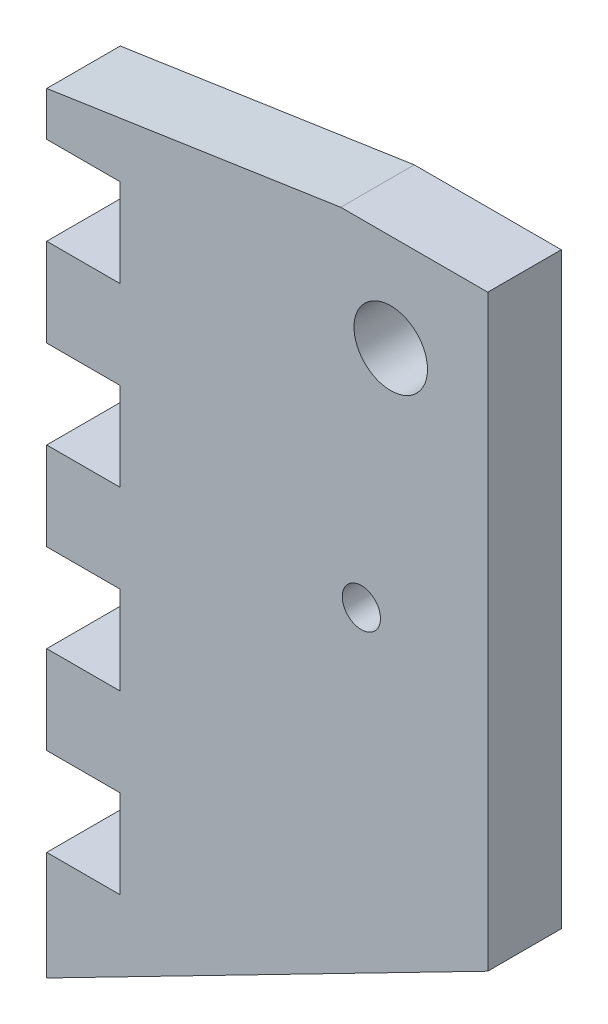
SolidWorks part; units mm, degrees
ref_plane "Front Plane" through (0, 0, 0) normal (0, 0, 1) x (1, 0, 0)
ref_plane "Top Plane" through (0, 0, 0) normal (0, 1, 0) x (1, 0, 0)
ref_plane "Right Plane" through (0, 0, 0) normal (1, 0, 0) x (0, 0, -1)
sketch "Sketch1" plane through (0, 0, 0) normal (0, 0, 1) x (1, 0, 0)
  line L0 (0, 0) -> (-38.1, 0)
  line L1 (0, 0) -> (0, -50.8)
  line L2 (-38.1, 0) -> (-38.1, -7.62)
  line L3 (-38.1, -7.62) -> (-31.75, -7.62)
  line L4 (-31.75, -7.62) -> (-31.75, -15.24)
  line L5 (-31.75, -15.24) -> (-38.1, -15.24)
  line L6 (-38.1, -45.72) -> (-38.1, -70.358)
  line L7 (-38.1, -15.24) -> (-38.1, -22.86)
  line L8 (-38.1, -22.86) -> (-31.75, -22.86)
  line L9 (-31.75, -22.86) -> (-31.75, -30.48)
  line L10 (-31.75, -30.48) -> (-38.1, -30.48)
  line L11 (-38.1, -30.48) -> (-38.1, -38.1)
  line L12 (-38.1, -38.1) -> (-31.75, -38.1)
  line L13 (-31.75, -38.1) -> (-31.75, -45.72)
  line L14 (-31.75, -45.72) -> (-38.1, -45.72)
  line L15 (-38.1, -70.358) -> (0, -50.8)
  circle A0 centre (-8.382, -8.382) radius 3.175
  dimension "D9" = 6.35
  dimension "D1" = 38.1
  dimension "D2" = 50.8
  dimension "D3" = 7.62
  dimension "D4" = 7.62
  dimension "D5" = 6.35
  dimension "D6" = 6.35
  dimension "D8" = 70.358
  dimension "D12" = 8.382
  dimension "D13" = 8.382
  dimension "D7" = 3
extrude "Boss-Extrude1" add sketch "Sketch1" along normal blind 6.35 contours L6 L15 L1 L0 L2 L3 L4 L5 L7 L8 L9 L10 L11 L12 L13 L14 A0 region at (-19.2374, -31.1465, 0)
sketch "Sketch2" plane through (0, 0, 0) normal (0, 0, -1) x (-1, 0, 0)
  line L5 (38.1, 0) -> (12.7, 0)
  line L6 (0, 0) -> (38.1, 0) construction
  line L7 (12.7, 0) -> (38.1, -3.81)
  line L8 (38.1, 0) -> (38.1, -7.62) construction
  line L9 (38.1, -3.81) -> (38.1, 0)
  dimension "D1" = 25.4
  dimension "D2" = 3.81
extrude "Cut-Extrude1" cut sketch "Sketch2" against normal blind 8.636
sketch "Sketch4" plane through (0, 0, 6.35) normal (0, 0, 1) x (1, 0, 0)
  line L0 (-38.1, -45.72) -> (-38.1, -53.34)
  line L1 (-38.1, -45.72) -> (-38.1, -70.358) construction
  line L2 (-38.1, -53.34) -> (-31.75, -53.34)
  line L3 (-31.75, -53.34) -> (-31.75, -60.96)
  line L4 (-31.75, -60.96) -> (-38.1, -60.96)
  line L5 (-38.1, -60.96) -> (-38.1, -53.34)
  line M18 (-38.1, -45.72) -> (-38.1, -70.358)
  dimension "D1" = 7.62
  dimension "D2" = 6.35
  dimension "D3" = 6.35
  dimension "D4" = 7.62
extrude "Cut-Extrude2" cut sketch "Sketch4" against normal through all contours L4 L3 L2 M18 region at (-34.925, -57.15, 6.35)
sketch "Sketch5" plane through (0, 0, 0) normal (0, 0, -1) x (-1, 0, 0)
  line L0 (8.382, -8.382) -> (10.9203, -29.0548) construction
  line L1 (8.382, -8.382) -> (8.382, -39.2411) construction
  circle A0 centre (8.382, -8.382) radius 3.175 construction
  circle A1 centre (10.9203, -29.0548) radius 1.651
  dimension "D1" = 20.828
  dimension "D2" = 7
extrude "Cut-Extrude4" cut sketch "Sketch5" against normal up to surface (6.35 mm away) up to face at (-5.207, -8.382, 6.35)
